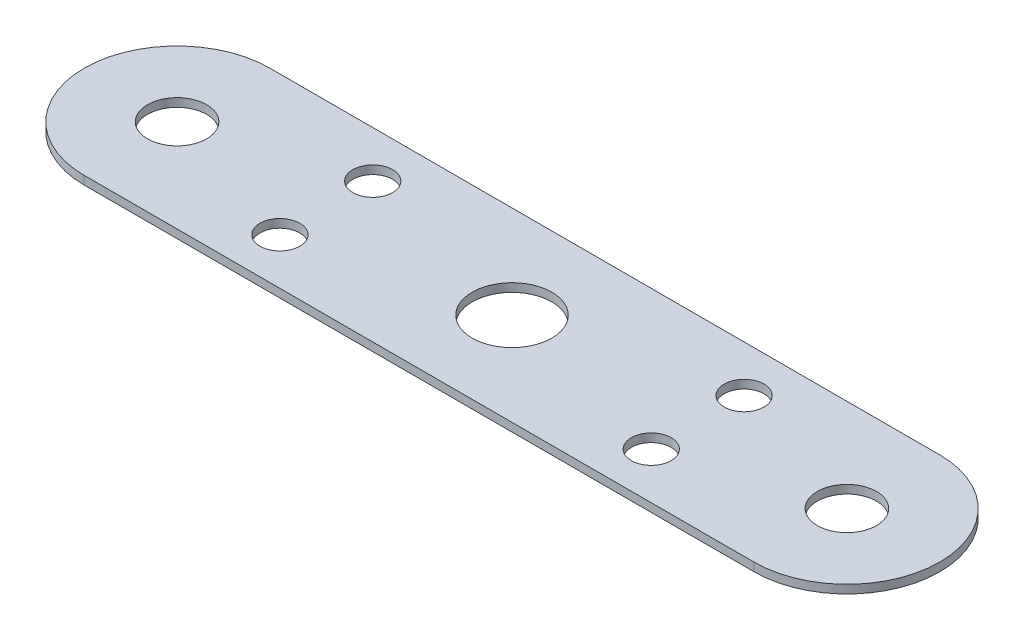
SolidWorks part; units mm, degrees
ref_plane "Front Plane" through (0, 0, 0) normal (0, 0, 1) x (1, 0, 0)
ref_plane "Top Plane" through (0, 0, 0) normal (0, 1, 0) x (1, 0, 0)
ref_plane "Right Plane" through (0, 0, 0) normal (1, 0, 0) x (0, 0, -1)
sketch "Sketch1" plane through (0, 0, 0) normal (0, 1, 0) x (1, 0, 0)
  line L0 (126.2582, 0) -> (-126.2582, 0)
  line L1 (-126.2582, 35) -> (126.2582, 35)
  line L3 (-126.2582, -35) -> (126.2582, -35)
  line L4 (-70, 35) -> (-70, 0) construction
  line L5 (-70, 0) -> (-70, -35) construction
  line L6 (70, 35) -> (70, 0) construction
  line L7 (70, 0) -> (70, -35) construction
  circle A0 centre (-126.2582, 0) radius 35
  circle A1 centre (126.2582, 0) radius 35
  circle A2 centre (-126.2582, 0) radius 11.15
  circle A3 centre (126.2582, 0) radius 11.15
  circle A4 centre (0, 0) radius 15
  circle A5 centre (-70, -17.5) radius 7.5
  circle A6 centre (-70, 17.5) radius 7.5
  circle A7 centre (70, 17.5) radius 7.5
  circle A8 centre (70, -17.5) radius 7.5
  point P4 (0, 0)
  dimension "D1" = 22.3
  dimension "D2" = 30
  dimension "D3" = 70
  dimension "D4" = 15
  dimension "D5" = 70
  dimension "D6" = 70
extrude "Boss-Extrude1" add sketch "Sketch1" along normal blind 3.175 contours A2 A0 | A4 L0 A0 L3 A1 | A4 L0 A1 L1 A0 | A3 A1 region at (0, 0, -18.9541) region at (-102.2095, 0, 24.0487) region at (0, 0, 18.9541) region at (150.307, 0, -24.0487)
